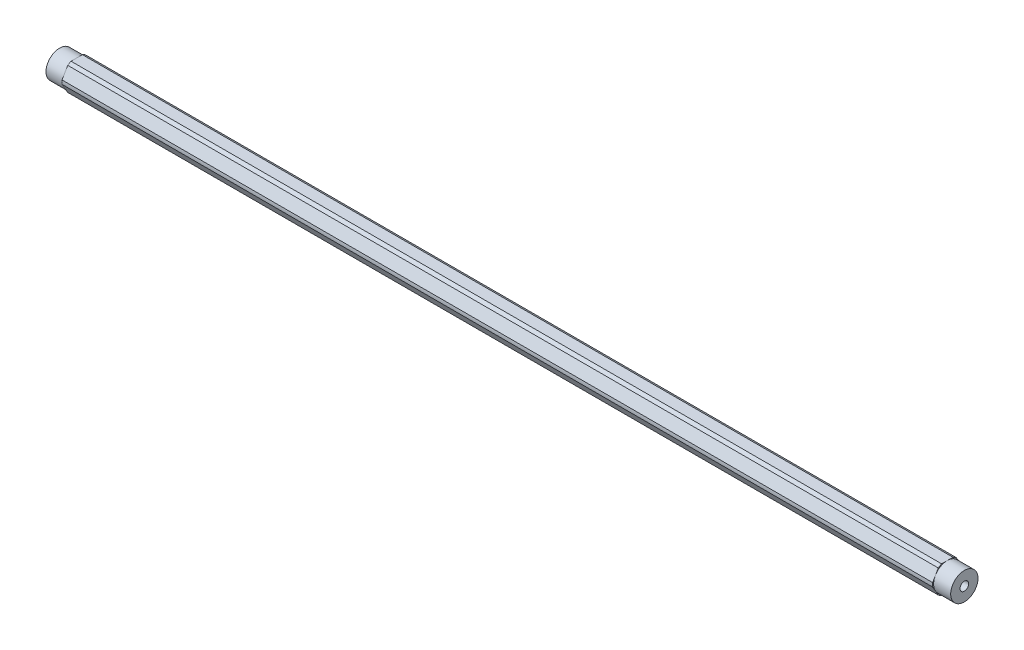
SolidWorks part; units mm, degrees
material "7075-T6 (SN)"
ref_plane "Front Plane" through (0, 0, 0) normal (0, 0, 1) x (1, 0, 0)
ref_plane "Top Plane" through (0, 0, 0) normal (0, 1, 0) x (1, 0, 0)
ref_plane "Right Plane" through (0, 0, 0) normal (1, 0, 0) x (0, 0, -1)
sketch "Sketch1" plane through (0, 0, 0) normal (1, 0, 0) x (0, 0, -1)
  line L1 (3.6662, 6.35) -> (-3.6662, 6.35)
  line L2 (-3.6662, 6.35) -> (-7.3323, 0)
  line L3 (-7.3323, 0) -> (-3.6662, -6.35)
  line L4 (-3.6662, -6.35) -> (3.6662, -6.35)
  line L5 (3.6662, -6.35) -> (7.3323, 0)
  line L6 (7.3323, 0) -> (3.6662, 6.35)
  circle A0 centre (0, 0) radius 2.0193
  circle A1 centre (0, 0) radius 6.875
  circle A2 centre (0, 0) radius 6.35 construction
  dimension "D1" = 13.75
  dimension "D2" = 4.0386
  dimension "D3" = 12.7
extrude "Boss-Extrude1" add sketch "Sketch1" along normal mid plane 420.6875 contours L6 A1 L1 L2 L3 L4 L5 A0 region at (0, 5.7918, -3.3439)
sketch "Sketch2" plane through (210.3438, 0, 0) normal (1, 0, 0) x (0, 0, -1)
  circle A0 centre (0, 0) radius 6.35
  dimension "D1" = 12.7
extrude "Cut-Extrude-Thin1" cut sketch "Sketch2" against normal blind 7.9375 thin thin type one direction wall 2.54
mirror "Mirror1" about plane through (0, 0, 0) normal (1, 0, 0) of "Cut-Extrude-Thin1"
equation "\"D1@Sketch1\"=13.75mm"
